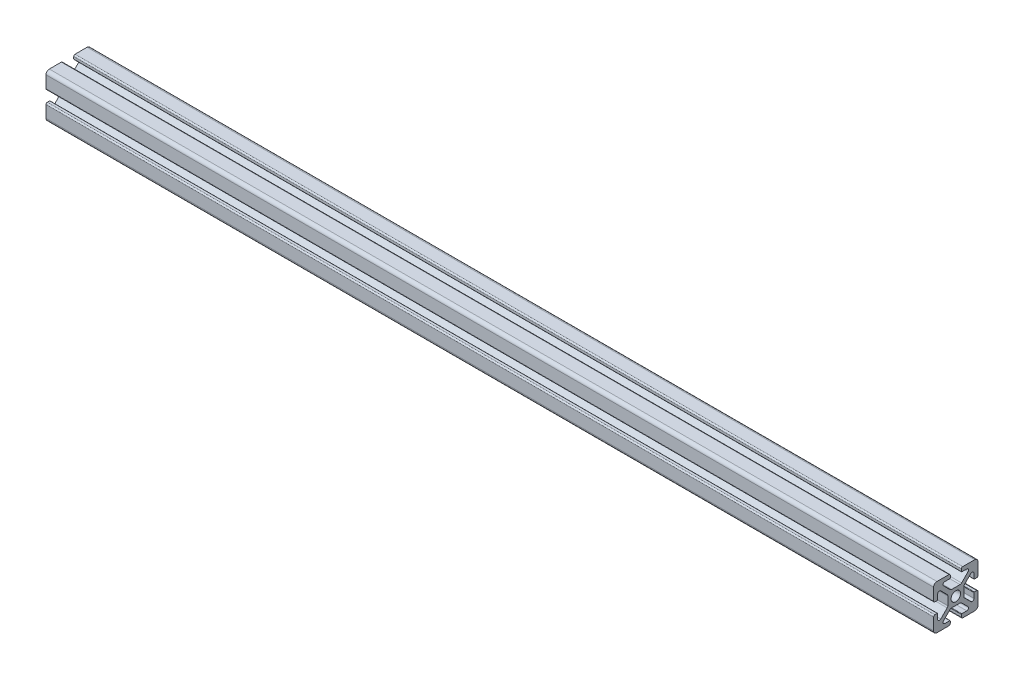
SolidWorks part; units mm, degrees
ref_plane "Front Plane" through (0, 0, 0) normal (0, 0, 1) x (1, 0, 0)
ref_plane "Top Plane" through (0, 0, 0) normal (0, 1, 0) x (1, 0, 0)
ref_plane "Right Plane" through (0, 0, 0) normal (1, 0, 0) x (0, 0, -1)
sketch "Sketch1" plane through (0, 0, 0) normal (1, 0, 0) x (0, 0, -1)
  line L0 (0, -10) -> (0, 10) construction
  line L1 (10, -10) -> (-10, -10)
  line L2 (10, -10) -> (10, 10)
  line L3 (10, 10) -> (0, 10)
  line L4 (-10, -10) -> (-10, 10)
  line L5 (10, -10) -> (-10, 10) construction
  line L6 (10, 10) -> (-10, -10) construction
  line L7 (10, 0) -> (-10, 0) construction
  line L8 (-2.5, 9.4) -> (-2.5, 8.3731)
  line L9 (-2.7, 8.1731) -> (-4.95, 8.1731)
  line L10 (-5.5157, 6.8075) -> (-2.6011, 3.8929)
  line L11 (-1.894, 3.6) -> (0, 3.6)
  line L12 (-5.3502, 4.0584) -> (-4.0584, 5.3502) construction
  line L13 (-3.825, 8.1731) -> (-3.825, 10) construction
  line L14 (-3.1, 10) -> (-10, 10)
  line L15 (-5.75, 7.3731) -> (5.75, 7.3731) construction
  circle A0 centre (0, 0) radius 2.15
  arc A1 (-4.95, 8.1731) -> (-5.5157, 6.8075) centre (-4.95, 7.3731) ccw
  arc A2 (-2.6011, 3.8929) -> (-1.894, 3.6) centre (-1.894, 4.6) ccw
  arc A3 (-2.5, 8.3731) -> (-2.7, 8.1731) centre (-2.7, 8.3731) cw
  arc A4 (-2.5, 9.4) -> (-3.1, 10) centre (-3.1, 9.4) ccw
  point P0 (0, 0)
  point P9 (0, 0)
  point P12 (0, 0)
  point P22 (-4.7043, 4.7043)
  point P32 (-2.5, 10)
  point P33 (-2.5, 8.8866)
  point P35 (-4.0584, 5.3502)
  point P37 (0, 7.3731)
  dimension "Center Hole Diameter" = 4.3
  dimension "D4" = 1
  dimension "D5" = 0.2
  dimension "D6" = 0.6
  dimension "D3" = 0.8
  dimension "Rail Height" = 20
  dimension "D7" = 6.4
  dimension "T Slot Width" = 5
  dimension "D10" = 10
  dimension "Rail Width" = 20
  dimension "D2" = 11.5
sketch "Sketch2" plane through (0, 0, 0) normal (0, 0, 1) x (1, 0, 0)
  line L0 (-132.4, 10) -> (-132.4, -10) construction
  line L1 (152.4, -10) -> (-152.4, -10) construction
  line L2 (152.4, -10) -> (152.4, 10) construction
  line L3 (152.4, 10) -> (-152.4, 10) construction
  line L4 (-152.4, -10) -> (-152.4, 10) construction
  line L5 (152.4, -10) -> (-152.4, 10) construction
  line L6 (152.4, 10) -> (-152.4, -10) construction
  line L7 (132.4, 10) -> (132.4, -10) construction
  point P0 (0, 0)
  point P12 (132.4, 0)
  dimension "Length" = 304.8
  dimension "D1" = 20
  dimension "D2" = 20
sketch "Sketch3" plane through (0, 0, 0) normal (1, 0, 0) x (0, 0, -1)
  line L0 (-5.5157, 6.8075) -> (-2.6011, 3.8929) construction
  line L5 (-3.1, 10) -> (-10, 10) construction
  line L6 (-2.5, 9.4) -> (-2.5, 8.3731) construction
  line L7 (-2.7, 8.1731) -> (-4.95, 8.1731) construction
  line L8 (-1.894, 3.6) -> (0, 3.6) construction
  line L9 (-5.5157, 6.8075) -> (-2.6011, 3.8929)
  line L10 (-10, 10) -> (0, 0) construction
  line L12 (-3.6, 1.894) -> (-3.6, 0)
  line L13 (-8.1731, 2.7) -> (-8.1731, 4.95)
  line L14 (-3.1, 10) -> (-8.5, 10)
  line L15 (-2.5, 9.4) -> (-2.5, 8.3731)
  line L16 (-2.7, 8.1731) -> (-4.95, 8.1731)
  line L17 (-1.894, 3.6) -> (0, 3.6)
  line L18 (-9.4, 2.5) -> (-8.3731, 2.5)
  line L19 (-10, 3.1) -> (-10, 8.5)
  line L20 (-6.8075, 5.5157) -> (-3.8929, 2.6011)
  line L21 (-3.6, 0) -> (-2.15, 0)
  line L22 (0, 3.6) -> (0, 2.15)
  arc A0 (-2.5, 9.4) -> (-3.1, 10) centre (-3.1, 9.4) ccw construction
  arc A1 (-2.7, 8.1731) -> (-2.5, 8.3731) centre (-2.7, 8.3731) ccw construction
  arc A2 (-4.95, 8.1731) -> (-5.5157, 6.8075) centre (-4.95, 7.3731) ccw construction
  arc A3 (-2.6011, 3.8929) -> (-1.894, 3.6) centre (-1.894, 4.6) ccw construction
  arc A4 (-2.5, 9.4) -> (-3.1, 10) centre (-3.1, 9.4) ccw
  arc A5 (-2.7, 8.1731) -> (-2.5, 8.3731) centre (-2.7, 8.3731) ccw
  arc A6 (-4.95, 8.1731) -> (-5.5157, 6.8075) centre (-4.95, 7.3731) ccw
  arc A7 (-2.6011, 3.8929) -> (-1.894, 3.6) centre (-1.894, 4.6) ccw
  arc A8 (-3.8929, 2.6011) -> (-3.6, 1.894) centre (-4.6, 1.894) cw
  arc A9 (-8.1731, 4.95) -> (-6.8075, 5.5157) centre (-7.3731, 4.95) cw
  arc A10 (-8.1731, 2.7) -> (-8.3731, 2.5) centre (-8.3731, 2.7) cw
  arc A11 (-9.4, 2.5) -> (-10, 3.1) centre (-9.4, 3.1) cw
  circle A12 centre (0, 0) radius 2.15 construction
  arc A13 (0, 2.15) -> (-2.15, 0) centre (0, 0) ccw
  arc A14 (-10, 8.5) -> (-8.5, 10) centre (-8.5, 8.5) cw
  dimension "D1" = 1.5
extrude "Boss-Extrude1" add sketch "Sketch3" against normal blind 200 and the other way blind 200
mirror "Mirror1" about plane through (0, 0, 0) normal (0, 1, 0) of bodies 104
mirror "Mirror2" about plane through (0, 0, 0) normal (0, 0, 1) of bodies 105
equation "\"D10@Sketch1\" = \"Rail Height@Sketch1\" / 2"
equation "\"D2@Sketch2\"=\"D1@Sketch2\""
